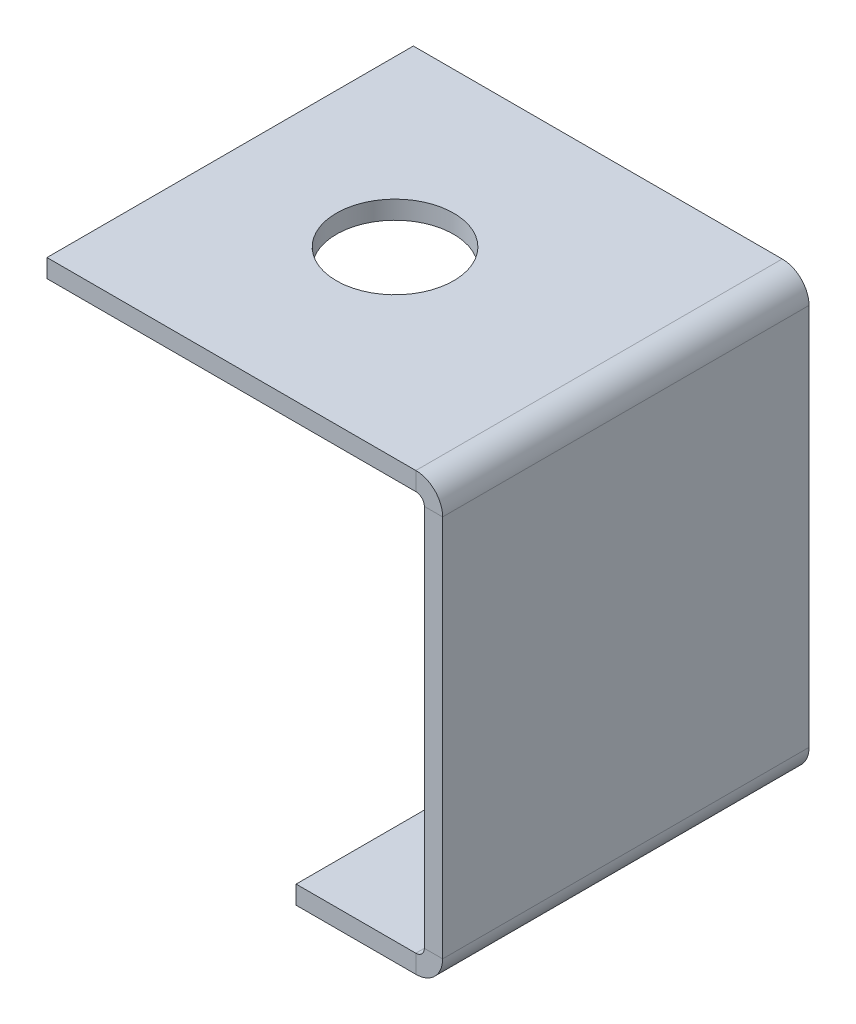
SolidWorks part; units mm, degrees
note: The reader was unsure of these and kept them because the rebuilt part matched: flange length of "Fuse to Stack", "Stack Base".
material "Copper"
ref_plane "Front Plane" through (0, 0, 0) normal (0, 0, 1) x (1, 0, 0)
ref_plane "Top Plane" through (0, 0, 0) normal (0, 1, 0) x (1, 0, 0)
ref_plane "Right Plane" through (0, 0, 0) normal (1, 0, 0) x (0, 0, -1)
sketch "Sketch1" plane through (0, 0, 0) normal (0, 1, 0) x (1, 0, 0)
  line L1 (0, 0) -> (32.7025, 0)
  line L2 (0, 0) -> (0, -31.75)
  line L3 (0, -31.75) -> (32.7025, -31.75)
  line L4 (32.7025, 0) -> (32.7025, -31.75)
  circle A0 centre (14.2875, -15.875) radius 5.08
  point P7 (0, -15.875)
  dimension "D3" = 10.16
  dimension "D1" = 31.75
  dimension "D2" = 32.7025
  dimension "D4" = 14.2875
base flange "HV Fuse Base" sketch "Sketch1" thickness 1.5875 reverse thickness direction no parameters "D1"=0.7366
edge flange "Fuse to Stack" sketch "Sketch8" flange angle 90 flange length 37.8155 flange position material outside bend radius 0.7366 thickness 1.5875 relief rectangular parameters "D6"=10
sketch "Sketch8" plane through (32.7025, -1.5875, 0) normal (1, 0, 0) x (0, 0, 1)
  line L0 (31.75, 0) -> (0, 0) construction
  line L1 (31.75, 0) -> (0, 0)
  line L2 (0, 0) -> (0, 36.228)
  line L3 (0, 36.228) -> (31.75, 36.228)
  line L4 (31.75, 36.228) -> (31.75, 0)
bend "EdgeBend1" bend radius 0.7366 bend angle 90 parameters "D5"=1
edge flange "Stack Base" sketch "Sketch11" flange angle 90 flange length 12.7 flange position material inside bend radius 0.7366 thickness 1.5875 relief rectangular parameters "D6"=10
sketch "Sketch11" plane through (32.7025, -37.8155, 0) normal (0, -1, 0) x (0, 0, 1)
  line L2 (0, 0) -> (0, 11.1125)
  line L3 (0, 11.1125) -> (31.75, 11.1125)
  line L4 (31.75, 11.1125) -> (31.75, 0)
  line L5 (31.75, 0) -> (0, 0) construction
  line L6 (31.75, 0) -> (0, 0)
bend "EdgeBend2" bend radius 0.7366 bend angle 90 parameters "D5"=2
sketch "Bend-Lines1" [suppressed] plane through (0, 0, 0) normal (0, 1, 0) x (1, 0, 0)
sketch "Bounding-Box1" [suppressed] plane through (0, 0, 0) normal (0, 1, 0) x (1, 0, 0)
sheet metal parameters "Sheet-Metal1" thickness 1.5875 parameters "D1"=0.7366
flat pattern "Flat-Pattern1" [suppressed]
sketch "Bend-Lines2" plane through (0, 0, 0) normal (0, 1, 0) x (1, 0, 0)
sketch3d "Bounding-Box2" [suppressed]
  line L0 (36.195, -31.75, 0) -> (0, -31.75, 0) construction
  line L1 (36.195, 0, 0) -> (0, 0, 0) construction
  line L2 (36.195, -31.75, 0) -> (36.195, 0, 0) construction
  line L3 (0, -31.75, 0) -> (0, 0, 0) construction
sheet metal parameters "Sheet-Metal2" thickness 1.5875 parameters "D1"=0.7366
flat pattern "Flat-Pattern1"
sketch "Bend-Lines2" plane through (0, 0, 0) normal (0, 1, 0) x (1, 0, 0)
  line L0 (36.6603, -31.75) -> (36.6603, 0) construction
  line L1 (36.6603, -31.75) -> (36.6603, 0) construction
sketch3d "Bounding-Box2" [suppressed]
  line L0 (56.7218, -31.75, 0) -> (0, -31.75, 0) construction
  line L1 (56.7218, 0, 0) -> (0, 0, 0) construction
  line L2 (56.7218, -31.75, 0) -> (56.7218, 0, 0) construction
  line L3 (0, -31.75, 0) -> (0, 0, 0) construction
bend of the flat pattern "Flatten-<EdgeBend1>1"
sheet metal parameters "Sheet-Metal3" thickness 1.5875 parameters "D1"=0.7366
flat pattern "Flat-Pattern1"
sketch "Bend-Lines2" plane through (0, 0, 0) normal (0, 1, 0) x (1, 0, 0)
  line L0 (33.1678, -31.75) -> (33.1678, 0) construction
  line L1 (33.1678, -31.75) -> (33.1678, 0) construction
  line L2 (68.739, -31.75) -> (68.739, 0) construction
  line L3 (68.739, -31.75) -> (68.739, 0) construction
sketch3d "Bounding-Box2" [suppressed]
  line L0 (80.3169, -31.75, 0) -> (0, -31.75, 0) construction
  line L1 (80.3169, 0, 0) -> (0, 0, 0) construction
  line L2 (80.3169, -31.75, 0) -> (80.3169, 0, 0) construction
  line L3 (0, -31.75, 0) -> (0, 0, 0) construction
bend of the flat pattern "Flatten-<EdgeBend1>1"
bend of the flat pattern "Flatten-<EdgeBend2>1"
